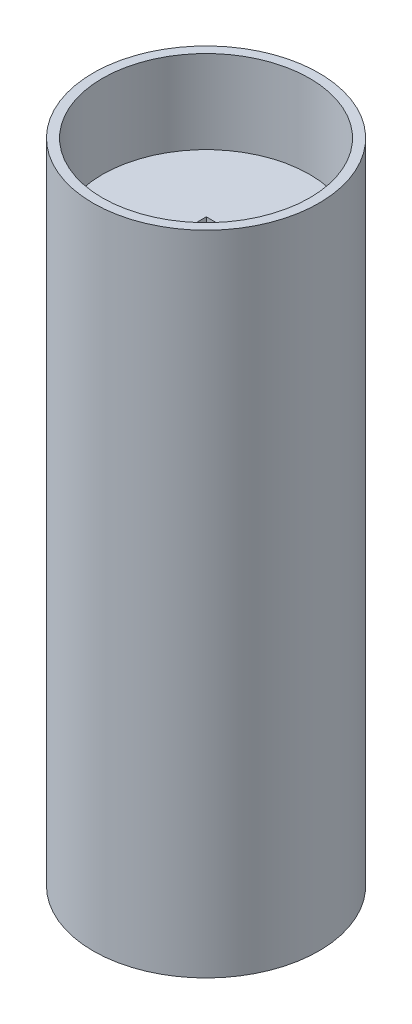
SolidWorks part; units mm, degrees
ref_plane "Front Plane" through (0, 0, 0) normal (0, 0, 1) x (1, 0, 0)
ref_plane "Top Plane" through (0, 0, 0) normal (0, 1, 0) x (1, 0, 0)
ref_plane "Right Plane" through (0, 0, 0) normal (1, 0, 0) x (0, 0, -1)
sketch "Sketch1" plane through (0, 0, 0) normal (0, 1, 0) x (1, 0, 0)
  circle A0 centre (0, 0) radius 61
  circle A1 centre (0, 0) radius 56
extrude "Boss-Extrude1" add sketch "Sketch1" along normal blind 300 contours A0 A1 region at (-59.2747, 0, 0)
ref_plane "Plane1" through (0, -20, 0) normal (0, 1, 0) x (1, 0, 0)
sketch "Sketch3" plane through (0, -20, 0) normal (0, 1, 0) x (1, 0, 0)
  circle A0 centre (0, 0) radius 56
extrude "Boss-Extrude2" add sketch "Sketch3" along normal blind 5
sketch "Sketch4" plane through (0, -20, 0) normal (0, -1, 0) x (1, 0, 0)
  circle A0 centre (-3, 0) radius 1.5
  circle A3 centre (3, 0) radius 1.5
  dimension "D1" = 3
  dimension "D2" = 3
  dimension "D3" = 6
extrude "Cut-Extrude1" [suppressed] cut sketch "Sketch4" against normal up to next
ref_plane "Plane2" through (0, 250, 0) normal (0, 1, 0) x (1, 0, 0)
sketch "Sketch5" plane through (0, 250, 0) normal (0, 1, 0) x (1, 0, 0)
  circle A0 centre (0, 0) radius 56
extrude "Boss-Extrude3" add sketch "Sketch5" along normal blind 5
sketch "Sketch6" plane through (0, 255, 0) normal (0, 1, 0) x (1, 0, 0)
  line L1 (-8.075, 8.215) -> (8.075, 8.215)
  line L2 (-8.075, 8.215) -> (-8.075, -8.215)
  line L3 (-8.075, -8.215) -> (8.075, -8.215)
  line L4 (8.075, 8.215) -> (8.075, -8.215)
  line L5 (-8.075, 8.215) -> (8.075, -8.215) construction
  line L6 (-8.075, -8.215) -> (8.075, 8.215) construction
  point P0 (0, 0)
  dimension "D1" = 16.15
  dimension "D2" = 16.43
extrude "Cut-Extrude2" cut sketch "Sketch6" against normal up to next (5 mm away)
extrude "Boss-Extrude4" add sketch "Sketch1<3>" against normal blind 50
sketch "Sketch1<3>" plane through (0, 0, 0) normal (0, 1, 0) x (1, 0, 0) same geometry as "Sketch1"
